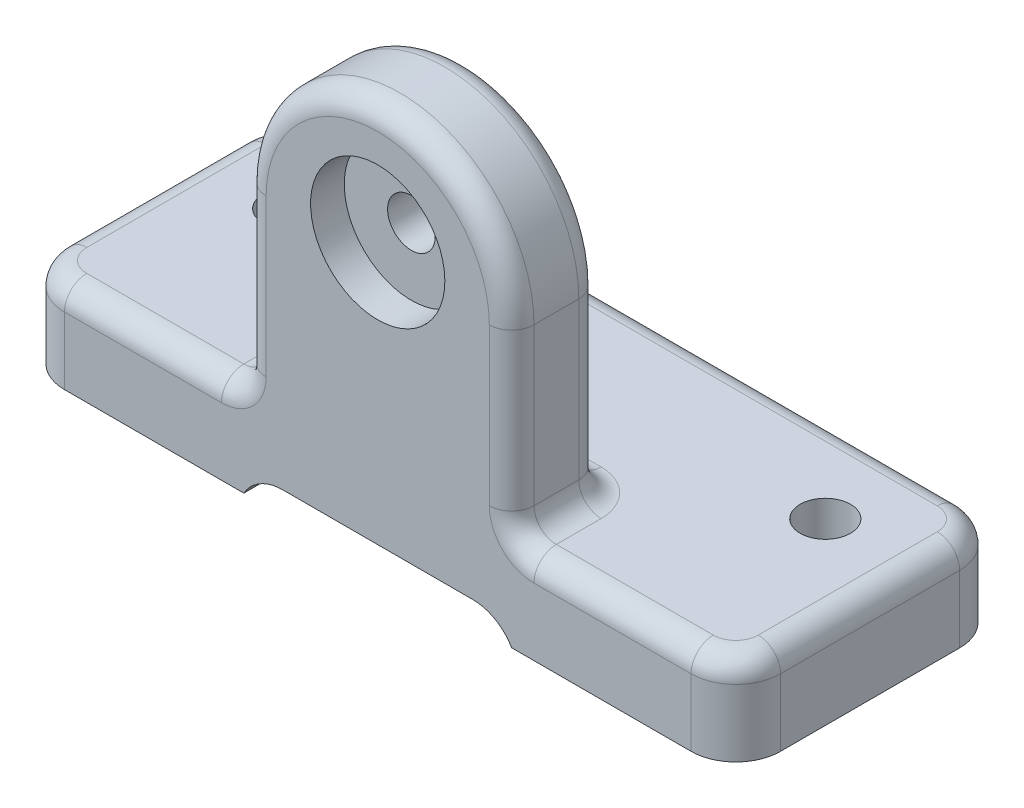
SolidWorks part; units mm, degrees
ref_plane "Front Plane" through (0, 0, 0) normal (0, 0, 1) x (1, 0, 0)
ref_plane "Top Plane" through (0, 0, 0) normal (0, 1, 0) x (1, 0, 0)
ref_plane "Right Plane" through (0, 0, 0) normal (1, 0, 0) x (0, 0, -1)
sketch "Sketch1" plane through (0, 0, 0) normal (0, 1, 0) x (1, 0, 0)
  line L1 (0, 0) -> (101.6, 0)
  line L2 (0, 0) -> (0, 38.1)
  line L3 (0, 38.1) -> (101.6, 38.1)
  line L4 (101.6, 0) -> (101.6, 38.1)
  dimension "D1" = 101.6
  dimension "D2" = 38.1
extrude "BasePlate" add sketch "Sketch1" along normal blind 12.7
sketch "Sketch3" plane through (0, 0, 0) normal (0, 0, 1) x (1, 0, 0)
  line L0 (31.8, 0) -> (31.8, 38.1)
  line L1 (0, 0) -> (101.6, 0) construction
  line L2 (69.8, 38.1) -> (69.8, 0)
  line L3 (0, 12.7) -> (0, 0) construction
  line L8 (0, 0) -> (101.6, 0)
  line L9 (101.6, 0) -> (101.6, 12.7)
  line L10 (101.6, 12.7) -> (0, 12.7)
  line L11 (0, 12.7) -> (0, 0)
  line L12 (31.8, 0) -> (69.8, 0)
  arc A0 (31.8, 38.1) -> (69.8, 38.1) centre (50.8, 38.1) cw
  dimension "D1" = 19
  dimension "D2" = 38.1
  dimension "D3" = 50.8
  dimension "D4" = 0
extrude "VertBoss" add sketch "Sketch3" against normal blind 12.7
hole_wizard "9/32 (0.28125) Diameter Hole1" positions "Sketch4" profile "Sketch5" hole size "9/32" standard "ANSI Inch" end condition through all
sketch "Sketch4" plane through (0, 12.7, 0) normal (0, 1, 0) x (1, 0, 0)
  line L0 (0, 38.1) -> (0, 0) construction
  line L1 (101.6, 0) -> (101.6, 38.1) construction
  line L2 (101.6, 38.1) -> (0, 38.1) construction
  point P0 (88.9, 25.4)
  point P2 (12.7, 25.4)
  dimension "D1" = 12.7
  dimension "D2" = 12.7
  dimension "D3" = 12.7
  dimension "D4" = 12.7
sketch "Sketch5" plane through (88.9, 12.7, -25.4) normal (1, 0, 0) x (0, 0, 1)
  line L0 (0, 0) -> (0, 12.7)
  line L1 (0, 12.7) -> (3.5719, 12.7)
  line L2 (3.5719, 12.7) -> (3.5719, 0)
  line L5 (3.5719, 0) -> (0, 0)
  line L11 (0, -6.35) -> (0, 107.95) construction
  dimension "Thru Hole Dia." = 7.1437
  dimension "Thru Hole Depth" = 12.7
hole_wizard "CBORE for 1/4 Hex Head Bolt1" positions "Sketch9" profile "Sketch10" counterbore size "1/4" standard "ANSI Inch" end condition through all
sketch "Sketch9" plane through (0, 0, 0) normal (0, 0, 1) x (1, 0, 0)
  point P0 (50.8, 40.3182)
sketch "Sketch10" plane through (50.8, 40.3182, 0) normal (1, 0, 0) x (0, -1, 0)
  line L0 (0, 0) -> (0, 38.1)
  line L1 (0, 38.1) -> (3.3782, 38.1)
  line L3 (3.3782, 38.1) -> (3.3782, 4.7752)
  line L4 (3.3782, 4.7752) -> (9.525, 4.7752)
  line L5 (9.525, 4.7752) -> (9.525, 0)
  line L7 (9.525, 0) -> (0, 0)
  line L11 (0, -6.35) -> (0, 107.95) construction
  dimension "Thru Hole Dia." = 6.7564
  dimension "Thru Hole Depth" = 38.1
  dimension "C'Bore Dia." = 19.05
  dimension "C'Bore Depth" = 4.7752
sketch "Sketch11" plane through (0, 0, 0) normal (0, 0, 1) x (1, 0, 0)
  line L0 (0, 0) -> (101.6, 0) construction
  line L1 (31.8, 0) -> (69.8, 0)
  line L2 (31.8, 0) -> (31.8, 3.17)
  line L3 (31.8, 3.17) -> (69.8, 3.17)
  line L4 (69.8, 0) -> (69.8, 3.17)
  line L5 (31.8, 38.1) -> (31.8, 12.7) construction
  line L6 (69.8, 12.7) -> (69.8, 38.1) construction
  dimension "D1" = 3.17
extrude "BottomSlot" cut sketch "Sketch11" against normal through all
fillet "Fillet1" radius 6.35 6 edges at (69.8, 3.17, -19.05) (31.8, 3.17, -19.05) (0, 6.35, -38.1) (0, 6.35, 0) (101.6, 6.35, -38.1) (101.6, 6.35, 0)
fillet "Fillet2" radius 3.17 18 edges at (31.8, 12.7, -6.35) (69.8, 12.7, -6.35) (50.8, 12.7, -12.7) (69.8, 25.4, -12.7) (31.8, 25.4, -12.7) (50.8, 57.1, -12.7) (1.8599, 12.7, -36.2401) (0, 12.7, -19.05) (1.8599, 12.7, -1.8599) (50.8, 12.7, -38.1) (99.7401, 12.7, -36.2401) (101.6, 12.7, -19.05) (99.7401, 12.7, -1.8599) (82.525, 12.7, 0) (19.075, 12.7, 0) (69.8, 25.4, 0) (31.8, 25.4, 0) (50.8, 57.1, 0)
